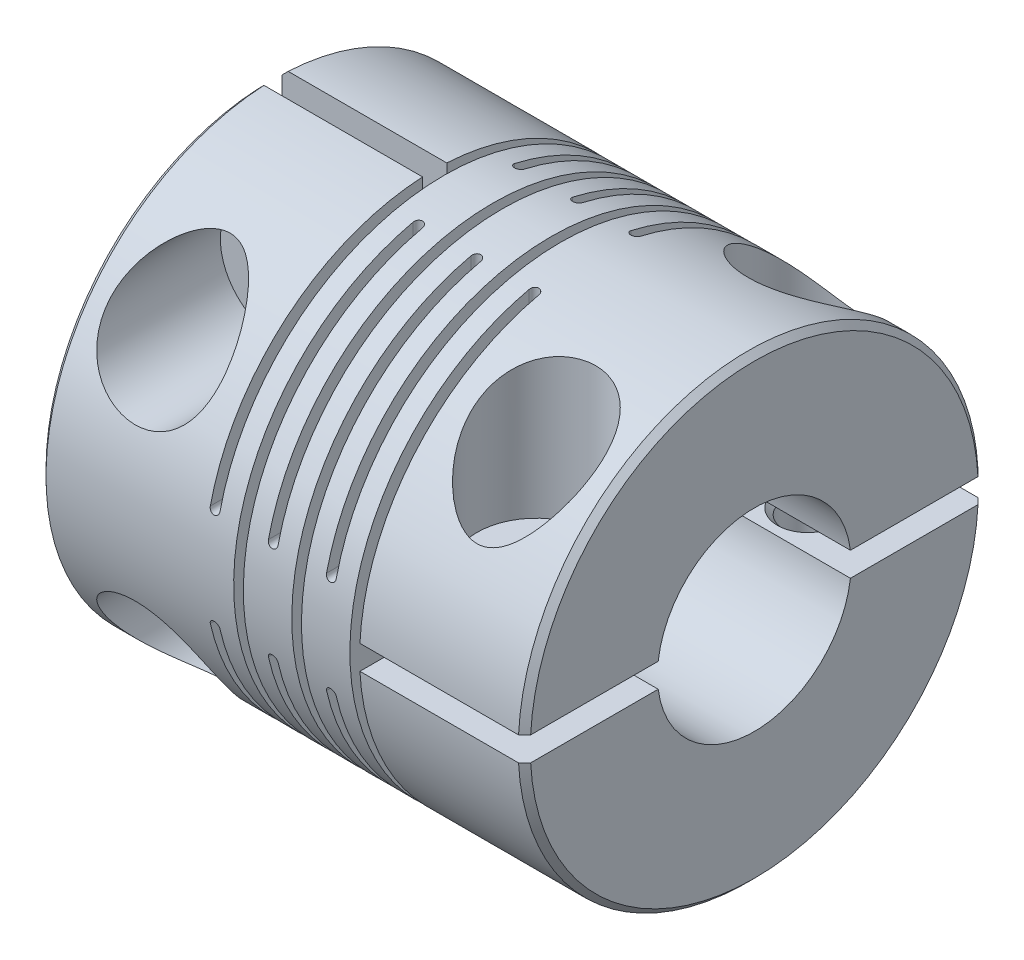
SolidWorks part; units mm, degrees
ref_plane "Front Plane" through (0, 0, 0) normal (0, 0, 1) x (1, 0, 0)
ref_plane "Top Plane" through (0, 0, 0) normal (0, 1, 0) x (1, 0, 0)
ref_plane "Right Plane" through (0, 0, 0) normal (1, 0, 0) x (0, 0, -1)
ref_plane "Plane1" through (0, 0, 0) normal (0, 0, 1) x (1, 0, 0)
sketch "Sketch1" plane through (0, 0, 0) normal (0, 0, 1) x (1, 0, 0)
  line L0 (0, 9.25) -> (0, 2.5)
  line L1 (0, 2.5) -> (6.8, 2.5)
  line L2 (6.8, 2.5) -> (6.8, 4.25)
  line L3 (6.8, 4.25) -> (13.2, 4.25)
  line L4 (13.2, 4.25) -> (13.2, 4)
  line L5 (13.2, 4) -> (20, 4)
  line L6 (20, 4) -> (20, 9.25)
  line L7 (20, 9.25) -> (19.75, 9.5)
  line L8 (19.75, 9.5) -> (0.25, 9.5)
  line L9 (0.25, 9.5) -> (0, 9.25)
  line L10 (20, 0) -> (0, 0) construction
revolve "Revolve1" add sketch "Sketch1" angle 360 about L10 reverse direction yes
ref_plane "Plane2" through (0, 0, 0) normal (0, 0, 1) x (1, 0, 0)
sketch "Sketch2" plane through (0, 0, 0) normal (0, 0, 1) x (1, 0, 0)
  line L0 (6.8, -10) -> (12, -10)
  line L1 (12, -10) -> (12, -2.1)
  line L2 (11.6, -2.1) -> (11.6, -9.75)
  line L3 (11.6, -9.75) -> (9.6, -9.75)
  line L4 (9.6, -9.75) -> (9.6, -2.1)
  line L5 (9.2, -2.1) -> (9.2, -9.75)
  line L6 (9.2, -9.75) -> (7.2, -9.75)
  line L7 (7.2, -9.75) -> (7.2, -2.1)
  line L8 (6.8, -2.1) -> (6.8, -10)
  arc A0 (12, -2.1) -> (11.6, -2.1) centre (11.8, -2.1) ccw
  arc A1 (9.6, -2.1) -> (9.2, -2.1) centre (9.4, -2.1) ccw
  arc A2 (7.2, -2.1) -> (6.8, -2.1) centre (7, -2.1) ccw
extrude "Cut-Extrude1" cut sketch "Sketch2" against normal blind 10 and the other way blind 10
ref_plane "Plane3" through (0, 0, 0) normal (0, 0, 1) x (1, 0, 0)
sketch "Sketch3" plane through (0, 0, 0) normal (0, 0, 1) x (1, 0, 0)
  line L0 (6.8, 10) -> (6.8, 2.1)
  line L1 (7.2, 2.1) -> (7.2, 9.75)
  line L2 (7.2, 9.75) -> (9.2, 9.75)
  line L3 (9.2, 9.75) -> (9.2, 2.1)
  line L4 (9.6, 2.1) -> (9.6, 9.75)
  line L5 (9.6, 9.75) -> (11.6, 9.75)
  line L6 (11.6, 9.75) -> (11.6, 2.1)
  line L7 (12, 2.1) -> (12, 10)
  line L8 (12, 10) -> (6.8, 10)
  arc A0 (6.8, 2.1) -> (7.2, 2.1) centre (7, 2.1) ccw
  arc A1 (9.2, 2.1) -> (9.6, 2.1) centre (9.4, 2.1) ccw
  arc A2 (11.6, 2.1) -> (12, 2.1) centre (11.8, 2.1) ccw
extrude "Cut-Extrude2" cut sketch "Sketch3" against normal blind 10 and the other way blind 10
ref_plane "Plane4" through (0, 0, 0) normal (0, 1, 0) x (-1, 0, 0)
sketch "Sketch4" plane through (0, 0, 0) normal (0, 1, 0) x (-1, 0, 0)
  line L0 (-8, 10) -> (-13.2, 10)
  line L1 (-13.2, 10) -> (-13.2, 2.1)
  line L2 (-12.8, 2.1) -> (-12.8, 9.75)
  line L3 (-12.8, 9.75) -> (-10.8, 9.75)
  line L4 (-10.8, 9.75) -> (-10.8, 2.1)
  line L5 (-10.4, 2.1) -> (-10.4, 9.75)
  line L6 (-10.4, 9.75) -> (-8.4, 9.75)
  line L7 (-8.4, 9.75) -> (-8.4, 2.1)
  line L8 (-8, 2.1) -> (-8, 10)
  arc A0 (-13.2, 2.1) -> (-12.8, 2.1) centre (-13, 2.1) ccw
  arc A1 (-10.8, 2.1) -> (-10.4, 2.1) centre (-10.6, 2.1) ccw
  arc A2 (-8.4, 2.1) -> (-8, 2.1) centre (-8.2, 2.1) ccw
extrude "Cut-Extrude3" cut sketch "Sketch4" against normal blind 10 and the other way blind 10
ref_plane "Plane5" through (0, 0, 0) normal (0, 1, 0) x (-1, 0, 0)
sketch "Sketch5" plane through (0, 0, 0) normal (0, 1, 0) x (-1, 0, 0)
  line L0 (-8, -10) -> (-8, -2.1)
  line L1 (-8.4, -2.1) -> (-8.4, -9.75)
  line L2 (-8.4, -9.75) -> (-10.4, -9.75)
  line L3 (-10.4, -9.75) -> (-10.4, -2.1)
  line L4 (-10.8, -2.1) -> (-10.8, -9.75)
  line L5 (-10.8, -9.75) -> (-12.8, -9.75)
  line L6 (-12.8, -9.75) -> (-12.8, -2.1)
  line L7 (-13.2, -2.1) -> (-13.2, -10)
  line L8 (-13.2, -10) -> (-8, -10)
  arc A0 (-8, -2.1) -> (-8.4, -2.1) centre (-8.2, -2.1) ccw
  arc A1 (-10.4, -2.1) -> (-10.8, -2.1) centre (-10.6, -2.1) ccw
  arc A2 (-12.8, -2.1) -> (-13.2, -2.1) centre (-13, -2.1) ccw
extrude "Cut-Extrude4" cut sketch "Sketch5" against normal blind 10 and the other way blind 10
ref_plane "Plane6" through (0, 0, 0) normal (1, 0, 0) x (0, 0, -1)
sketch "Sketch6" plane through (0, 0, 0) normal (1, 0, 0) x (0, 0, -1)
  line L0 (-0.5, 9.7) -> (-0.5, -9.7)
  line L1 (-0.5, -9.7) -> (0.5, -9.7)
  line L2 (0.5, -9.7) -> (0.5, 9.7)
  line L3 (0.5, 9.7) -> (-0.5, 9.7)
extrude "Cut-Extrude5" cut sketch "Sketch6" along normal blind 6.8
ref_plane "Plane7" through (20, 0, 0) normal (1, 0, 0) x (0, 0, -1)
sketch "Sketch7" plane through (20, 0, 0) normal (1, 0, 0) x (0, 0, -1)
  line L0 (-9.7, 0.5) -> (-9.7, -0.5)
  line L1 (-9.7, -0.5) -> (9.7, -0.5)
  line L2 (9.7, -0.5) -> (9.7, 0.5)
  line L3 (9.7, 0.5) -> (-9.7, 0.5)
extrude "Cut-Extrude6" cut sketch "Sketch7" against normal blind 6.8
ref_plane "Plane8" through (3.4, 0, 0) normal (1, 0, 0) x (0, 0, -1)
sketch "Sketch8" plane through (3.4, 0, 0) normal (1, 0, 0) x (0, 0, -1)
  line L0 (-9.5, 5.6) -> (-9.5, 8.05)
  line L1 (-9.5, 8.05) -> (-3, 8.05)
  line L2 (-3, 8.05) -> (-3, 6.85)
  line L3 (-3, 6.85) -> (0.5, 6.85)
  line L4 (0.5, 6.85) -> (0.7435, 6.6065)
  line L5 (0.7435, 6.6065) -> (4.7565, 6.6065)
  line L6 (4.7565, 6.6065) -> (5, 6.85)
  line L7 (5, 6.85) -> (9.5, 6.85)
  line L8 (9.5, 6.85) -> (9.5, 5.6)
  line L9 (9.5, 5.6) -> (-9.5, 5.6)
  line L10 (9.5, 5.6) -> (-9.5, 5.6) construction
revolve "Cut-Revolve1" cut sketch "Sketch8" angle 360 about L10 reverse direction yes
ref_plane "Plane9" through (3.4, 0, 0) normal (1, 0, 0) x (0, 0, -1)
sketch "Sketch9" plane through (3.4, 0, 0) normal (1, 0, 0) x (0, 0, -1)
  line L0 (-9.5, -5.6) -> (-9.5, -3.15)
  line L1 (-9.5, -3.15) -> (-3, -3.15)
  line L2 (-3, -3.15) -> (-3, -4.35)
  line L3 (-3, -4.35) -> (0.5, -4.35)
  line L4 (0.5, -4.35) -> (0.7435, -4.5935)
  line L5 (0.7435, -4.5935) -> (4.7565, -4.5935)
  line L6 (4.7565, -4.5935) -> (5, -4.35)
  line L7 (5, -4.35) -> (9.5, -4.35)
  line L8 (9.5, -4.35) -> (9.5, -5.6)
  line L9 (9.5, -5.6) -> (-9.5, -5.6)
  line L10 (9.5, -5.6) -> (-9.5, -5.6) construction
revolve "Cut-Revolve2" cut sketch "Sketch9" angle 360 about L10 reverse direction yes
ref_plane "Plane10" through (16.6, 0, 0) normal (1, 0, 0) x (0, 0, -1)
sketch "Sketch10" plane through (16.6, 0, 0) normal (1, 0, 0) x (0, 0, -1)
  line L0 (-5.6, -9.5) -> (-6.85, -9.5)
  line L1 (-6.85, -9.5) -> (-6.85, -5)
  line L2 (-6.85, -5) -> (-6.6065, -4.7565)
  line L3 (-6.6065, -4.7565) -> (-6.6065, -0.7435)
  line L4 (-6.6065, -0.7435) -> (-6.85, -0.5)
  line L5 (-6.85, -0.5) -> (-6.85, 3)
  line L6 (-6.85, 3) -> (-8.05, 3)
  line L7 (-8.05, 3) -> (-8.05, 9.5)
  line L8 (-8.05, 9.5) -> (-5.6, 9.5)
  line L9 (-5.6, 9.5) -> (-5.6, -9.5)
  line L10 (-5.6, 9.5) -> (-5.6, -9.5) construction
revolve "Cut-Revolve3" cut sketch "Sketch10" angle 360 about L10 reverse direction yes
ref_plane "Plane11" through (16.6, 0, 0) normal (1, 0, 0) x (0, 0, -1)
sketch "Sketch11" plane through (16.6, 0, 0) normal (1, 0, 0) x (0, 0, -1)
  line L0 (5.6, -9.5) -> (4.35, -9.5)
  line L1 (4.35, -9.5) -> (4.35, -5)
  line L2 (4.35, -5) -> (4.5935, -4.7565)
  line L3 (4.5935, -4.7565) -> (4.5935, -0.7435)
  line L4 (4.5935, -0.7435) -> (4.35, -0.5)
  line L5 (4.35, -0.5) -> (4.35, 3)
  line L6 (4.35, 3) -> (3.15, 3)
  line L7 (3.15, 3) -> (3.15, 9.5)
  line L8 (3.15, 9.5) -> (5.6, 9.5)
  line L9 (5.6, 9.5) -> (5.6, -9.5)
  line L10 (5.6, 9.5) -> (5.6, -9.5) construction
revolve "Cut-Revolve4" cut sketch "Sketch11" angle 360 about L10 reverse direction yes
